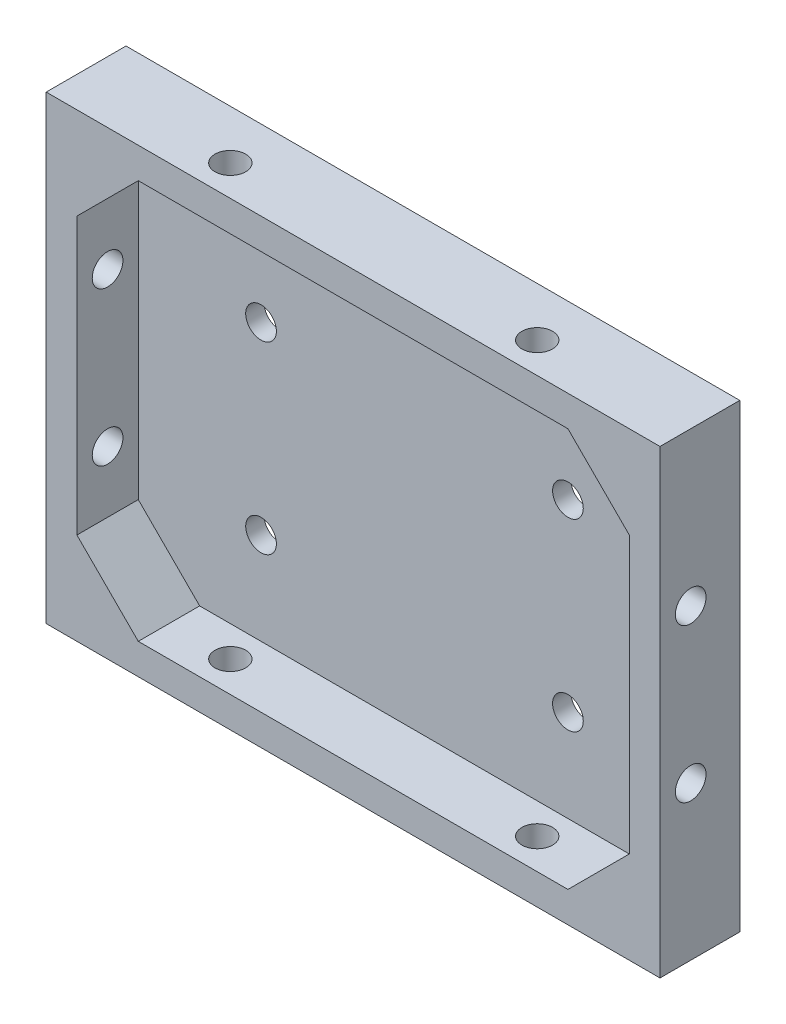
SolidWorks part; units mm, degrees
ref_plane "Plan de face" through (0, 0, 0) normal (0, 0, 1) x (1, 0, 0)
ref_plane "Plan de dessus" through (0, 0, 0) normal (0, 1, 0) x (1, 0, 0)
ref_plane "Plan de droite" through (0, 0, 0) normal (1, 0, 0) x (0, 0, -1)
sketch "Esquisse1" plane through (0, 0, 0) normal (0, 0, 1) x (1, 0, 0)
  line L0 (44.1184, 33.7284) -> (54.1184, 33.7284)
  line L1 (-45.8816, 33.7284) -> (44.1184, 33.7284)
  line L2 (-45.8816, 33.7284) -> (-45.8816, -41.2716)
  line L3 (-45.8816, -41.2716) -> (54.1184, -41.2716)
  line L4 (54.1184, 23.7284) -> (54.1184, -41.2716)
  line L5 (54.1184, 33.7284) -> (54.1184, 23.7284)
  point P6 (54.1184, 33.7284)
  dimension "D1" = 100
  dimension "D2" = 75
extrude "Boss.-Extru.1" add sketch "Esquisse1" along normal blind 13
shell "Coque1" thickness 5 removed face at (4.1184, -3.7716, 13)
sketch "Esquisse2" plane through (-45.8816, 0, 0) normal (-1, 0, 0) x (0, 0, 1)
  line L0 (13, 33.7284) -> (13, -41.2716) construction
  line L1 (13, 33.7284) -> (0, 33.7284) construction
  line L2 (13, -41.2716) -> (0, -41.2716) construction
  circle A0 centre (8, 8.7284) radius 2.5
  circle A1 centre (8, -16.2716) radius 2.5
  dimension "D1" = 5
  dimension "D2" = 5
  dimension "D3" = 5
  dimension "D4" = 5
  dimension "D5" = 25
  dimension "D6" = 25
extrude "Enlèv. mat.-Extru.1" cut sketch "Esquisse2" against normal up to surface (100 mm away) contours A1 | A0 region at (-45.8816, -16.2716, 8) up to face at (54.1184, -3.7716, 6.5)
sketch "Esquisse3" plane through (0, -41.2716, 0) normal (0, -1, 0) x (1, 0, 0)
  line L0 (-45.8816, 13) -> (54.1184, 13) construction
  line L2 (54.1184, 13) -> (54.1184, 0) construction
  line L3 (-45.8816, 13) -> (-45.8816, 0) construction
  circle A0 centre (-20.8816, 8) radius 2.5
  circle A1 centre (29.1184, 8) radius 2.5
  dimension "D1" = 5
  dimension "D2" = 5
  dimension "D3" = 5
  dimension "D4" = 5
  dimension "D5" = 25
  dimension "D6" = 25
extrude "Enlèv. mat.-Extru.2" cut sketch "Esquisse3" against normal up to surface (75 mm away) up to face at (4.1184, 33.7284, 6.5)
sketch "Esquisse4" plane through (0, 0, 3) normal (0, 0, 1) x (1, 0, 0)
  line L0 (-30.8816, 28.7284) -> (-40.8816, 18.7284)
  line L1 (49.1184, 28.7284) -> (-40.8816, 28.7284) construction
  line L2 (-40.8816, 28.7284) -> (-40.8816, -36.2716) construction
  line L3 (-40.8816, 18.7284) -> (-40.8816, 28.7284)
  line L4 (-40.8816, 28.7284) -> (-30.8816, 28.7284)
  line L5 (49.1184, 28.7284) -> (49.1184, 18.7284)
  line L6 (49.1184, -36.2716) -> (49.1184, 28.7284) construction
  line L7 (49.1184, 18.7284) -> (39.1184, 28.7284)
  line L8 (39.1184, 28.7284) -> (49.1184, 28.7284)
  line L9 (49.1184, 28.7284) -> (-40.8816, 28.7284) construction
  line L10 (49.1184, -36.2716) -> (49.1184, -26.2716)
  line L11 (49.1184, -26.2716) -> (39.1184, -36.2716)
  line L12 (-40.8816, -36.2716) -> (49.1184, -36.2716) construction
  line L13 (39.1184, -36.2716) -> (49.1184, -36.2716)
  line L14 (-30.8816, -36.2716) -> (-40.8816, -26.2716)
  line L15 (-40.8816, 28.7284) -> (-40.8816, -36.2716) construction
  line L16 (-40.8816, -26.2716) -> (-40.8816, -36.2716)
  line L17 (-40.8816, -36.2716) -> (-30.8816, -36.2716)
  dimension "D1" = 10
  dimension "D2" = 10
  dimension "D3" = 10
  dimension "D4" = 10
  dimension "D5" = 10
  dimension "D6" = 10
  dimension "D7" = 10
  dimension "D8" = 10
extrude "Boss.-Extru.2" add sketch "Esquisse4" along normal up to surface (10 mm away) up to face at (4.1184, -3.7716, 13)
sketch "Esquisse6" plane through (0, 0, 3) normal (0, 0, 1) x (1, 0, 0)
  line L0 (-45.8816, -41.2716) -> (54.1184, -41.2716) construction
  line L1 (54.1184, -41.2716) -> (54.1184, 33.7284) construction
  line L3 (-45.8816, 33.7284) -> (-45.8816, -41.2716) construction
  line L4 (54.1184, 33.7284) -> (-45.8816, 33.7284) construction
  circle A0 centre (-20.8816, -21.2716) radius 2.5
  circle A1 centre (29.1184, -21.2716) radius 2.5
  circle A2 centre (-20.8816, 8.7284) radius 2.5
  circle A3 centre (29.1184, 8.7284) radius 2.5
  circle A4 centre (39.1184, 19.6056) radius 5
  dimension "D2" = 5
  dimension "D3" = 5
  dimension "D4" = 25
  dimension "D6" = 20
  dimension "D8" = 25
  dimension "D9" = 10
  dimension "D7" = 5
  dimension "D12" = 5
  dimension "D5" = 20
  dimension "D10" = 25
  dimension "D11" = 25
  dimension "D13" = 25
  dimension "D14" = 25
  dimension "D15" = 15
extrude "Enlèv. mat.-Extru.3" cut sketch "Esquisse6" against normal up to surface (3 mm away) up to face at (4.1184, -3.7716, 0)
